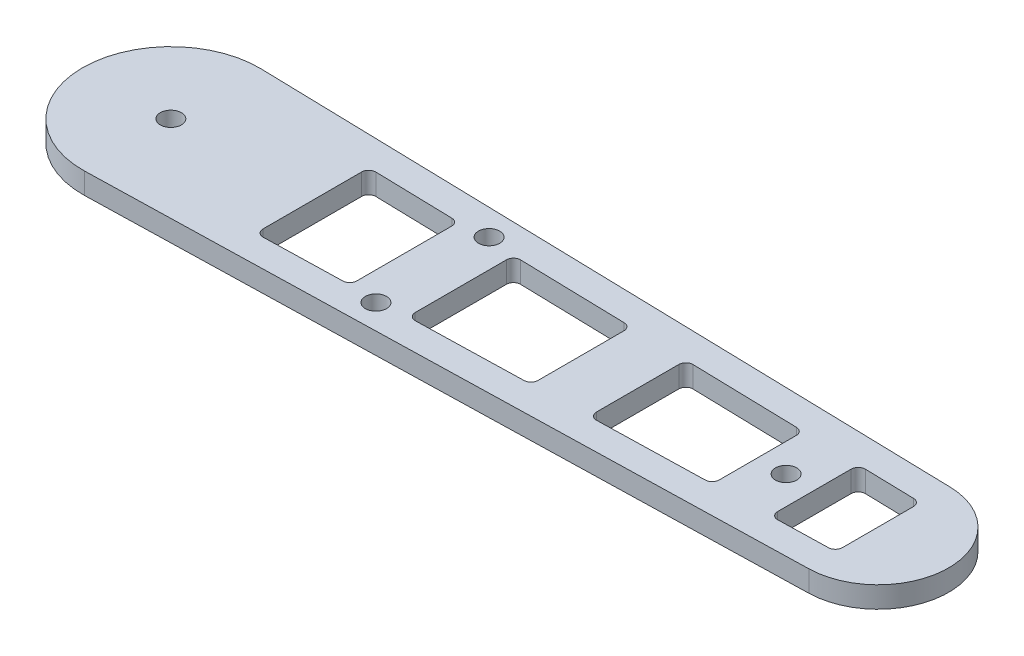
SolidWorks part; units mm, degrees
material "ABS"
ref_plane "前视基准面" through (0, 0, 0) normal (0, 0, 1) x (1, 0, 0)
ref_plane "上视基准面" through (0, 0, 0) normal (0, 1, 0) x (1, 0, 0)
ref_plane "右视基准面" through (0, 0, 0) normal (1, 0, 0) x (0, 0, -1)
sketch "草图1" plane through (0, 0, 0) normal (0, 1, 0) x (1, 0, 0)
  line L0 (-32.5011, 0) -> (135.0118, 0) construction
  line L1 (0.3125, 12.4961) -> (100.25, 9.9969)
  line L2 (0.3125, -12.4961) -> (100.25, -9.9969)
  circle A0 centre (0, 0) radius 12.5
  circle A1 centre (100, 0) radius 10
  circle A2 centre (0, 0) radius 1.5
  dimension "D1" = 25
  dimension "D2" = 20
  dimension "D4" = 3
  dimension "D3" = 100
extrude "凸台-拉伸1" add sketch "草图1" along normal blind 3 contours A0 L0 A2 | L0 A0 A2 | A0 L0 A1 L1 | L0 A0 L2 A1 | A1 L0 | L0 A1 region at (0, 0, -5.3734) region at (0, 0, 5.3734) region at (49.7914, 0, -5.8152) region at (49.7914, 0, 5.8152) region at (100, 0, -4.2441) region at (100, 0, 4.2441)
sketch "草图2" plane through (0, 0, 0) normal (0, -1, 0) x (1, 0, 0)
  circle A0 centre (0, 0) radius 3
  circle A1 centre (0, 0) radius 4.5
  dimension "D1" = 6
  dimension "D2" = 9
extrude "凸台-拉伸2" add sketch "草图2" along normal blind 2.5
sketch "草图3" plane through (0, 3, 0) normal (0, 1, 0) x (1, 0, 0)
  line L0 (-22.3979, 0) -> (134.9394, 0) construction
  line L1 (20, 8.0025) -> (20, -8.0025)
  line L2 (20, 8.0025) -> (100, 6.0019)
  line L5 (0.3125, 12.4961) -> (100.25, 9.9969) construction
  line L6 (20, -8.0025) -> (100, -6.0019)
  line L7 (100, 6.0019) -> (100, -6.0019)
  line L8 (33, 7.6774) -> (33, -7.6774)
  line L9 (58, 7.0522) -> (58, -7.0522)
  line L10 (66, 6.8521) -> (66, -6.8521)
  line L11 (41, 7.4773) -> (41, -7.4773)
  line L12 (83, 6.427) -> (83, -6.427)
  line L13 (91, 6.2269) -> (91, -6.2269)
  circle A1 centre (37, 8) radius 1.5
  circle A2 centre (37, -8) radius 1.5
  circle A3 centre (87, 0) radius 1.5
  dimension "D5" = 8
  dimension "D7" = 3
  dimension "D13" = 3
  dimension "D1" = 20
  dimension "D2" = 4
  dimension "D3" = 33
  dimension "D4" = 8
  dimension "D6" = 37
  dimension "D9" = 58
  dimension "D10" = 8
  dimension "D11" = 83
  dimension "D12" = 8
  dimension "D14" = 4
  dimension "D15" = 100
extrude "切除-拉伸1" cut sketch "草图3" against normal blind 3 contours L1 L0 L8 L2 | L0 L1 L6 L8 | L2 A1 | L2 A1 | A2 L6 | A2 L6 | L11 L0 L9 L2 | L0 L11 L6 L9 | L10 L0 L12 L2 | L0 L10 L6 L12 | A3 L0 | L0 A3 | L13 L0 L7 L2 | L0 L13 L6 L7 region at (26.4551, 3, -3.9205) region at (26.4551, 3, 3.9205) region at (49.4171, 3, -3.6334) region at (49.4171, 3, 3.6334) region at (37.0104, 3, -8.4153) region at (36.9782, 3, -7.1299) region at (36.9782, 3, 7.1299) region at (37.0104, 3, 8.4153) region at (74.4093, 3, -3.3209) region at (74.4093, 3, 3.3209) region at (87, 3, -0.6366) region at (87, 3, 0.6366) region at (95.4724, 3, -3.0576) region at (95.4724, 3, 3.0576)
fillet "圆角1" radius 1 16 edges at (91, 1.5, -6.2269) (91, 1.5, 6.2269) (100, 1.5, 6.0019) (100, 1.5, -6.0019) (83, 1.5, -6.427) (66, 1.5, -6.8521) (66, 1.5, 6.8521) (83, 1.5, 6.427) (58, 1.5, 7.0522) (41, 1.5, 7.4773) (58, 1.5, -7.0522) (41, 1.5, -7.4773) (33, 1.5, 7.6774) (33, 1.5, -7.6774) (20, 1.5, 8.0025) (20, 1.5, -8.0025)
sketch "草图4" plane through (0, 0, 0) normal (0, -1, 0) x (1, 0, 0)
  circle A0 centre (0, 0) radius 1.5
  circle A1 centre (0, 0) radius 3
extrude "凸台-拉伸3" add sketch "草图4" along normal blind 1
